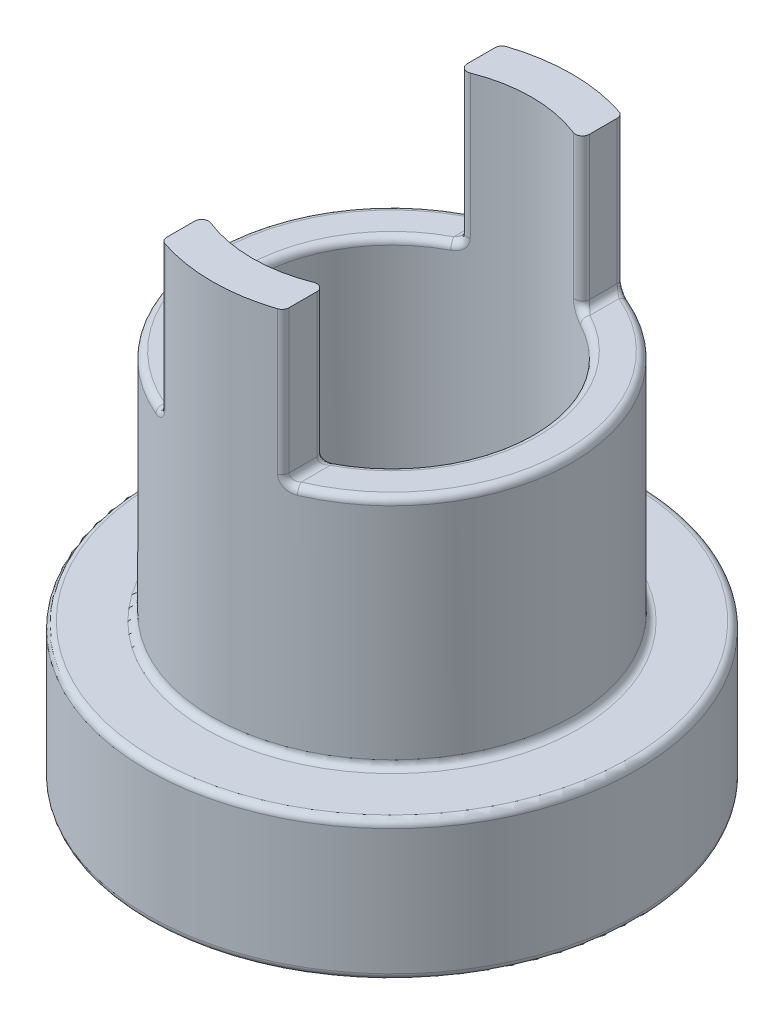
SolidWorks part; units mm, degrees
ref_plane "前视基准面" through (0, 0, 0) normal (0, 0, 1) x (1, 0, 0)
ref_plane "上视基准面" through (0, 0, 0) normal (0, 1, 0) x (1, 0, 0)
ref_plane "右视基准面" through (0, 0, 0) normal (1, 0, 0) x (0, 0, -1)
sketch "草图2" plane through (0, 0, 0) normal (0, 1, 0) x (1, 0, 0)
  circle A0 centre (0, 0) radius 4
  circle A1 centre (0, 0) radius 5.15
  circle A2 centre (0, 0) radius 7
  dimension "D1" = 14
  dimension "D2" = 10.3
  dimension "D3" = 8
extrude "凸台-拉伸1" add sketch "草图2" along normal blind 15 contours A1 A0 region at (-5.0043, 0, 0)
extrude "凸台-拉伸2" add sketch "草图2<3>" along normal blind 4 contours A2 A1 region at (-6.802, 0, 0)
sketch "草图2<3>" plane through (0, 0, 0) normal (0, 1, 0) x (1, 0, 0) same geometry as "草图2"
sketch "草图3" plane through (0, 0, 0) normal (0, 0, 1) x (1, 0, 0)
  line L0 (-10.2295, 0) -> (9.0862, 0) construction
  line L1 (-10.2295, 10.7) -> (9.0862, 10.7) construction
  line L2 (0, 17.7897) -> (0, -3.5719) construction
  line L3 (-1.75, 17.7897) -> (-1.75, -3.5719) construction
  line L4 (1.75, 17.7897) -> (1.75, -3.5719) construction
  line L6 (-1.75, 10.7) -> (-11.0117, 10.7)
  line L7 (-1.75, 10.7) -> (-1.75, 20.5275)
  line L8 (-1.75, 20.5275) -> (-11.0117, 20.5275)
  line L9 (-11.0117, 10.7) -> (-11.0117, 20.5275)
  line L10 (1.75, 10.7) -> (9.6277, 10.7)
  line L11 (1.75, 10.7) -> (1.75, 20.5275)
  line L12 (1.75, 20.5275) -> (9.6277, 20.5275)
  line L13 (9.6277, 10.7) -> (9.6277, 20.5275)
  point P11 (-5.15, 15)
  point P12 (5.15, 15)
  dimension "D1" = 10.7
  dimension "D2" = 1.75
  dimension "D3" = 1.75
extrude "切除-拉伸1" cut sketch "草图3" against normal through all both and the other way through all
fillet "圆角1" radius 0.2 20 edges at (-1.75, 12.85, 3.5969) (-1.75, 12.85, 4.8436) (-1.75, 12.85, -4.8436) (-1.75, 12.85, -3.5969) (1.75, 12.85, -4.8436) (1.75, 12.85, -3.5969) (1.75, 12.85, 4.8436) (1.75, 12.85, 3.5969) (-1.75, 10.7, 4.2202) (-5.15, 10.7, 0) (-1.75, 10.7, -4.2202) (-4, 10.7, 0) (1.75, 10.7, -4.2202) (5.15, 10.7, 0) (1.75, 10.7, 4.2202) (4, 10.7, 0) (0, 4, 7) (0, 4, 5.15) (0, 0, 7) (0, 0, 4)
